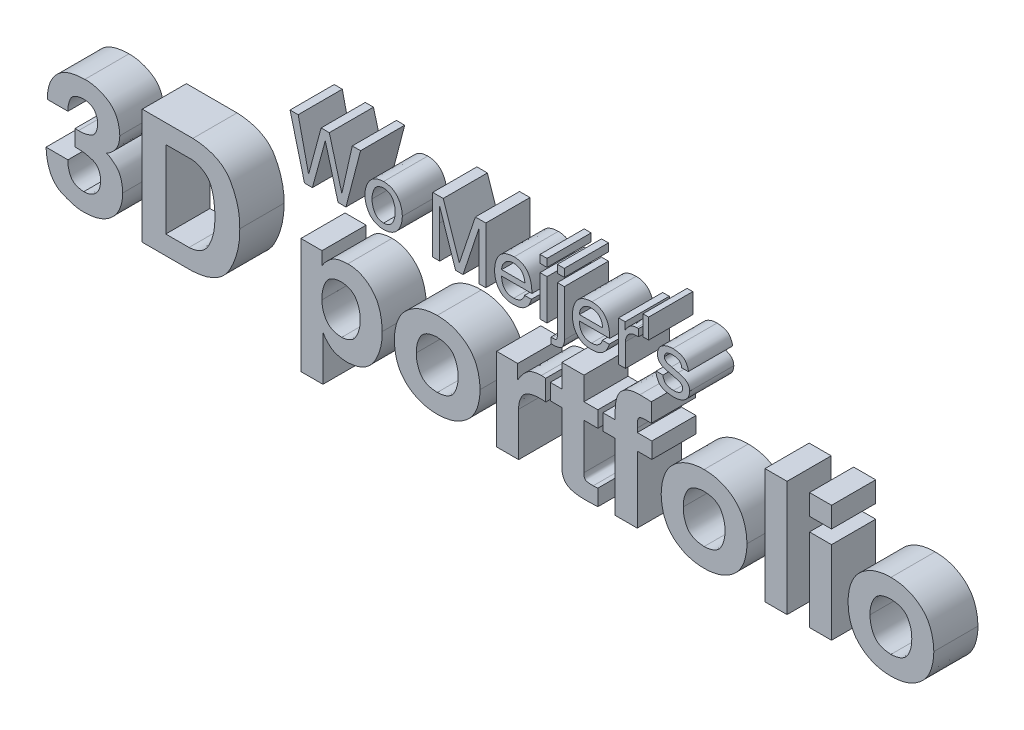
SolidWorks part; units mm, degrees
ref_plane "Front" through (0, 0, 0) normal (0, 0, 1) x (1, 0, 0)
ref_plane "Top" through (0, 0, 0) normal (0, 1, 0) x (1, 0, 0)
ref_plane "Right" through (0, 0, 0) normal (1, 0, 0) x (0, 0, -1)
sketch "Sketch1" plane through (0, 0, 0) normal (0, 0, 1) x (1, 0, 0)
  line L0 (-81.5898, 0) -> (81.5898, 0) construction
  line L1 (-59.0037, -15) -> (59.0037, -15) construction
  line L2 (0, 0) -> (0, -15) construction
  text T0 "Wo Meijer's" font "Helvetica CE" height 6.35
  text T1 "3D portfolio" font "Helvetica CE" height in points 48
  point P4 (0, 0)
  point P7 (0, 0)
  dimension "D1" = 15
extrude "Boss-Extrude1" add sketch "Sketch1" along normal blind 5
